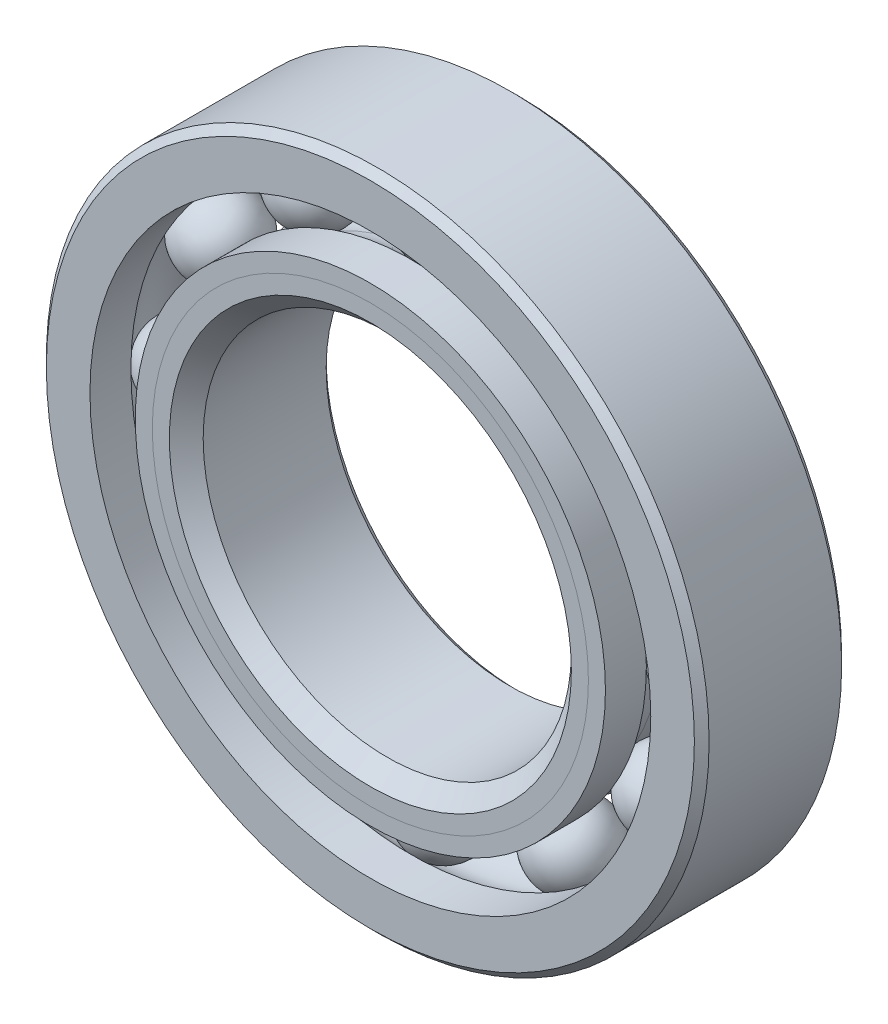
SolidWorks part; units mm, degrees
ref_plane "Front Plane" through (0, 0, 0) normal (0, 0, 1) x (1, 0, 0)
ref_plane "Top Plane" through (0, 0, 0) normal (0, 1, 0) x (1, 0, 0)
ref_plane "Right Plane" through (0, 0, 0) normal (1, 0, 0) x (0, 0, -1)
sketch "Sketch1" plane through (0, 0, 0) normal (1, 0, 0) x (0, 0, -1)
  line L0 (-3.175, 0) -> (3.175, 0) construction
  line L1 (0, 14.2875) -> (0, -14.2875) construction
  line L2 (2.8575, 14.2875) -> (-2.8575, 14.2875)
  line L3 (-2.8575, 14.2875) -> (-3.175, 13.97)
  line L4 (-3.175, 13.97) -> (-3.175, 12.0894)
  line L5 (-3.175, 12.0894) -> (-1.4111, 12.0894)
  line L6 (3.175, 12.0894) -> (1.4111, 12.0894)
  line L7 (3.175, 13.97) -> (3.175, 12.0894)
  line L8 (2.8575, 14.2875) -> (3.175, 13.97)
  line L9 (0, 14.2875) -> (0, 11.1125) construction
  line L10 (0, 11.1125) -> (0, 7.9375) construction
  arc A0 (-1.4111, 12.0894) -> (1.4111, 12.0894) centre (0, 11.1125) cw
  point P14 (0, 7.9375)
  dimension "Width" = 6.35
  dimension "OD" = 28.575
  dimension "D1" = 45
  dimension "D2" = 0.3175
  dimension "D3" = 2.8222
  dimension "D4" = 0.9769
revolve "Revolve1" add sketch "Sketch1" angle 360 about L0
sketch "Sketch2" plane through (0, 0, 0) normal (1, 0, 0) x (0, 0, -1)
  line L0 (-3.175, 10.1356) -> (-1.4111, 10.1356)
  line L1 (-3.175, 13.97) -> (-3.175, -13.97) construction
  line L2 (-3.175, 10.1356) -> (-3.175, 9.4012)
  line L3 (-3.175, 9.4012) -> (-2.4406, 8.6669)
  line L4 (-2.4406, 8.6669) -> (0, 8.6669)
  line L5 (0, 14.2875) -> (0, -14.2875) construction
  line L6 (0, 8.6669) -> (0, 9.3962)
  line L7 (0, 9.3962) -> (0, 7.9375) construction
  line L8 (-3.175, 10.1356) -> (-3.175, 8.6669) construction
  line L9 (-3.175, 8.6669) -> (-2.4406, 8.6669) construction
  arc A0 (-1.4111, 10.1356) -> (0, 9.3962) centre (0, 11.1125) ccw
  arc A1 (1.4111, 12.0894) -> (-1.4111, 12.0894) centre (0, 11.1125) ccw construction
  circle A2 centre (0, 11.1125) radius 1.7163 construction
  dimension "D1" = 45
revolve "Revolve2" add sketch "Sketch2" angle 360 about L0
sketch "Sketch3" plane through (0, 0, 0) normal (1, 0, 0) x (0, 0, -1)
  line L0 (-3.175, 9.4012) -> (-2.4406, 8.6669)
  line L1 (-2.4406, 8.6669) -> (0, 8.6669)
  line L2 (0, 8.6669) -> (0, 9.3962)
  line L3 (-3.175, 9.4012) -> (-3.175, 8.6669)
  line L4 (-3.175, 10.1356) -> (-3.175, 8.6669) construction
  line L5 (-3.175, 8.6669) -> (-2.4456, 7.9375)
  line L6 (-2.4456, 7.9375) -> (2.8575, 7.9375)
  line L7 (2.8575, 14.2875) -> (2.8575, -14.2875) construction
  line L8 (2.8575, 7.9375) -> (3.175, 8.255)
  line L9 (3.175, -13.97) -> (3.175, 13.97) construction
  line L10 (3.175, 8.255) -> (3.175, 10.1356)
  line L11 (3.175, 10.1356) -> (1.4111, 10.1356)
  line L13 (2.8575, 14.2875) -> (3.175, 13.97) construction
  circle A0 centre (0, 11.1125) radius 1.7163 construction
  arc A1 (1.4111, 10.1356) -> (0, 9.3962) centre (0, 11.1125) cw
revolve "Revolve3" add sketch "Sketch3" angle 360 about L0
sketch "Sketch4" plane through (0, 0, 0) normal (1, 0, 0) x (0, 0, -1)
  line L0 (-1.7163, 11.1125) -> (1.7163, 11.1125)
  circle A1 centre (0, 11.1125) radius 1.7163 construction
  arc A2 (-1.7163, 11.1125) -> (1.7163, 11.1125) centre (0, 11.1125) cw
  arc A3 (1.4111, 12.0894) -> (-1.4111, 12.0894) centre (0, 11.1125) ccw construction
revolve "Revolve4" add sketch "Sketch4" angle 360 about L0
ref_axis "Axis1" through (0, 0, -3.175) along (0, 0, 1)
pattern_circular "CirPattern1" count 12 every 30 about axis through (0, 0, -3.175) along (0, 0, 1) of bodies 104
equation "\"D2@Sketch1\" = \"Width@Sketch1\"*.05"
equation "\"D3@Sketch1\" = \"Width@Sketch1\"/2.25"
equation "\"D4@Sketch1\" = (((\"OD@Sketch1\"-\"Width@Sketch1\")/2)/3.25)/3.5"
equation "\"D2@CirPattern1\" = 360/\"Balls@CirPattern1\""
